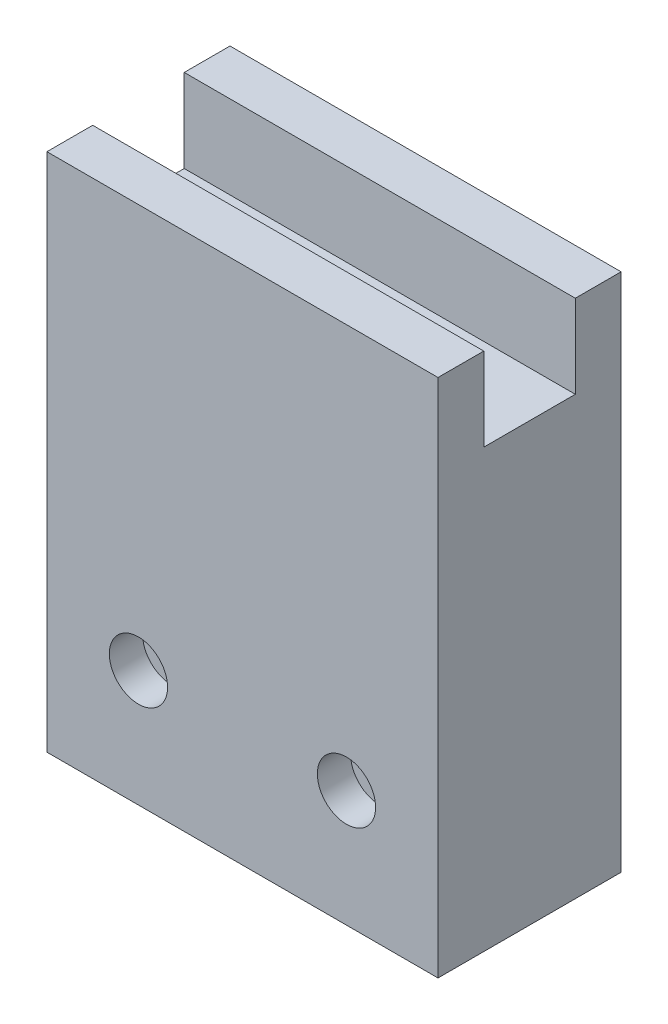
SolidWorks part; units mm, degrees
material "Alloy Steel"
ref_plane "Front Plane" through (0, 0, 0) normal (0, 0, 1) x (1, 0, 0)
ref_plane "Top Plane" through (0, 0, 0) normal (0, 1, 0) x (1, 0, 0)
ref_plane "Right Plane" through (0, 0, 0) normal (1, 0, 0) x (0, 0, -1)
sketch "Sketch1" plane through (0, 0, 0) normal (0, 0, 1) x (1, 0, 0)
  line L1 (0, 0) -> (-47, 0)
  line L2 (0, 0) -> (0, 62.5)
  line L3 (0, 62.5) -> (-47, 62.5)
  line L4 (-47, 0) -> (-47, 62.5)
  dimension "D1" = 62.5
  dimension "D2" = 47
extrude "Boss-Extrude1" add sketch "Sketch1" along normal blind 22
sketch "Sketch2" plane through (0, 62.5, 0) normal (0, 1, 0) x (1, 0, 0)
  line L0 (-47, -22) -> (-47, 0) construction
  line L1 (-53.5, -16.5) -> (6.5, -16.5)
  line L2 (-53.5, -16.5) -> (-53.5, -5.5)
  line L3 (-53.5, -5.5) -> (6.5, -5.5)
  line L4 (6.5, -16.5) -> (6.5, -5.5)
  line L5 (0, 0) -> (-47, 0) construction
  point P6 (-47, -11)
  point P7 (-53.5, -11)
  point P10 (-23.5, 0)
  point P11 (-23.5, -5.5)
  dimension "D1" = 11
  dimension "D2" = 60
extrude "Cut-Extrude1" cut sketch "Sketch2" against normal blind 10
sketch "Sketch3" plane through (0, 0, 22) normal (0, 0, 1) x (1, 0, 0)
  line L0 (-23.5, 62.5) -> (-23.5, 0) construction
  line L1 (0, 62.5) -> (-47, 62.5) construction
  line L2 (-47, 0) -> (0, 0) construction
  circle A0 centre (-36, 14) radius 2
  circle A1 centre (-36, 14) radius 3.5
  circle A2 centre (-11, 14) radius 2
  circle A3 centre (-11, 14) radius 3.5
  point P9 (0, 0)
  point P13 (0, 0)
  dimension "D1" = 4
  dimension "D2" = 7
  dimension "D3" = 14
  dimension "D4" = 25
extrude "Cut-Extrude2" cut sketch "Sketch3" against normal through all both and the other way through all contours A0 | A2 region at (-36, 14, 22) region at (-11, 14, 22)
extrude "Cut-Extrude3" cut sketch "Sketch3<3>" against normal blind 4 and the other way through all
sketch "Sketch3<3>" plane through (0, 0, 22) normal (0, 0, 1) x (1, 0, 0) same geometry as "Sketch3"
sketch "Sketch4" plane through (0, 0, 0) normal (0, -1, 0) x (1, 0, 0)
  line L0 (-23.5, 22) -> (-23.5, 0) construction
  line L1 (-47, 22) -> (0, 22) construction
  line L2 (-47, 0) -> (0, 0) construction
  line L3 (-47, 22) -> (-47, 0) construction
  circle A0 centre (-36, 11) radius 1.5
  circle A1 centre (-36, 11) radius 2.5
  circle A2 centre (-11, 11) radius 2.5
  circle A3 centre (-11, 11) radius 1.5
  point P12 (0, 0)
  point P15 (-47, 11)
  dimension "D1" = 3
  dimension "D2" = 5
  dimension "D3" = 12.5
extrude "Cut-Extrude6" cut sketch "Sketch4" along direction (0, 1, 0) on the side against the normal blind 13 contours A3 | A0 | A3 | A0 region at (-36, 0, 11) region at (-11, 0, 11)
extrude "Cut-Extrude7" cut sketch "Sketch4<3>" against normal blind 4 contours A1 A0 | A2 A3 region at (-38.4293, 0, 11) region at (-13.4293, 0, 11)
sketch "Sketch4<3>" plane through (0, 0, 0) normal (0, -1, 0) x (1, 0, 0) same geometry as "Sketch4"
